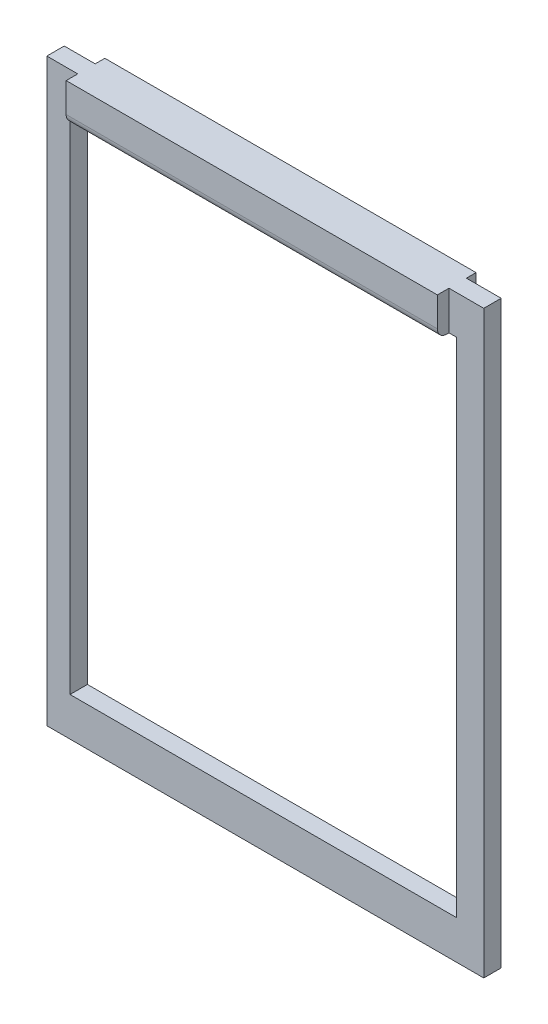
SolidWorks part; units mm, degrees
ref_plane "Front Plane" through (0, 0, 0) normal (0, 0, 1) x (1, 0, 0)
ref_plane "Top Plane" through (0, 0, 0) normal (0, 1, 0) x (1, 0, 0)
ref_plane "Right Plane" through (0, 0, 0) normal (1, 0, 0) x (0, 0, -1)
sketch "Sketch2" plane through (0, 0, 0) normal (0, 0, 1) x (1, 0, 0)
  line L0 (0, 0) -> (56.5, 0)
  line L1 (56.5, 0) -> (56.5, 75)
  line L2 (56.5, 75) -> (0, 75)
  line L3 (0, 75) -> (0, 0)
  line L4 (3, 70) -> (3, 5)
  line L5 (3, 5) -> (53, 5)
  line L6 (53, 5) -> (53, 70)
  line L7 (53, 70) -> (3, 70)
  dimension "D1" = 56.5
  dimension "D2" = 50
  dimension "D3" = 3
  dimension "D4" = 5
  dimension "D5" = 75
  dimension "D6" = 65
extrude "Boss-Extrude1" add sketch "Sketch2" along normal blind 2.25
sketch "Sketch3" plane through (0, 0, 2.25) normal (0, 0, 1) x (1, 0, 0)
  line L0 (56.5, 75) -> (0, 75) construction
  line L1 (52, 75) -> (4, 75)
  line L2 (52, 75) -> (52, 70)
  line L3 (52, 70) -> (4, 70)
  line L4 (4, 75) -> (4, 70)
  line L5 (53, 70) -> (3, 70) construction
  dimension "D1" = 48
  dimension "D2" = 1
extrude "Boss-Extrude2" add sketch "Sketch3" along normal blind 1.5 contours L4 L3 L2 L1
extrude "Boss-Extrude3" add sketch "Sketch3<4>" along normal blind 1.5 and the other way blind 3.5
sketch "Sketch3<4>" plane through (0, 0, 2.25) normal (0, 0, 1) x (1, 0, 0) same geometry as "Sketch3"
fillet "Fillet3" radius 1.2 2 edges at (28, 70, -1.25) (28, 70, 3.75)
